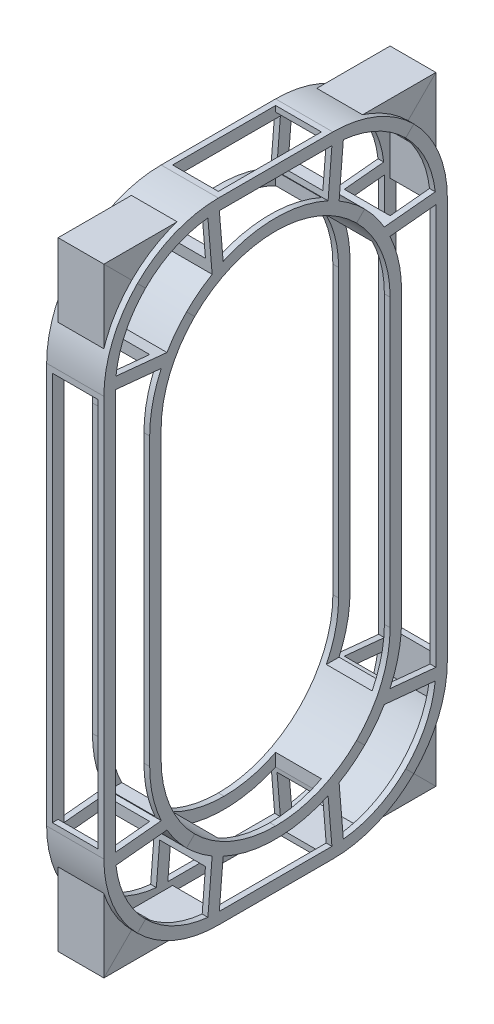
SolidWorks part; units mm, degrees
ref_plane "Front Plane" through (0, 0, 0) normal (0, 0, 1) x (1, 0, 0)
ref_plane "Top Plane" through (0, 0, 0) normal (0, 1, 0) x (1, 0, 0)
ref_plane "Right Plane" through (0, 0, 0) normal (1, 0, 0) x (0, 0, -1)
sketch "Sketch2" plane through (0, 0, 0) normal (0, 1, 0) x (1, 0, 0)
  line L0 (20, 20) -> (-20, 20)
  line L1 (25, -25) -> (-25, -25)
  line L2 (25, -25) -> (25, 25)
  line L3 (25, 25) -> (-25, 25)
  line L4 (-25, -25) -> (-25, 25)
  line L5 (25, -25) -> (-25, 25) construction
  line L6 (25, 25) -> (-25, -25) construction
  line L7 (-20, -20) -> (-20, 20)
  line L8 (20, -20) -> (-20, -20)
  line L9 (20, -20) -> (20, 20)
  point P0 (0, 0)
  dimension "D1" = 50
  dimension "D2" = 50
  dimension "D3" = 5
sketch "Sketch3" plane through (0, 0, 0) normal (1, 0, 0) x (0, 0, -1)
  line L0 (0, 0) -> (0, 500)
  line L2 (250, 500) -> (250, 0)
  line L3 (0, 500) -> (250, 500)
  line L4 (250, 0) -> (0, 0)
  dimension "D2" = 250
  dimension "D1" = 500
sweep "Sweep1" add profiles "Sketch2" path "Sketch3"
fillet "Fillet3" radius 100 8 edges at (0, 525, -275) (0, 25, -225) (0, -25, -275) (0, -25, 25) (0, 25, -25) (0, 475, -225) (0, 525, 25) (0, 475, -25)
sketch "Sketch5" plane through (0, -25, 0) normal (0, -1, 0) x (1, 0, 0)
  line L0 (-25, -125) -> (-17.5, -125) construction
  line L1 (-25, -175) -> (-25, -75) construction
  line L2 (25, -175) -> (25, -75) construction
  line L3 (0, -125) -> (25, -125) construction
  line L22 (-20, -170) -> (20, -170)
  line L23 (20, -170) -> (20, -80)
  line L24 (20, -80) -> (-20, -80)
  line L25 (-20, -80) -> (-20, -170)
  line L26 (-20, -170) -> (20, -170)
  line L27 (20, -170) -> (20, -80)
  line L28 (20, -80) -> (-20, -80)
  line L29 (-20, -80) -> (-20, -170)
  point P6 (0, -125)
  dimension "D1" = 5
extrude "Cut-Extrude2" cut sketch "Sketch5" against normal through all
sketch "Sketch6" plane through (0, 0, 25) normal (0, 0, 1) x (1, 0, 0)
  line L8 (-20, 420) -> (-20, 80)
  line L9 (-20, 80) -> (20, 80)
  line L10 (20, 80) -> (20, 420)
  line L11 (20, 420) -> (-20, 420)
  line L12 (-20, 420) -> (-20, 80)
  line L13 (-20, 80) -> (20, 80)
  line L14 (20, 80) -> (20, 420)
  line L15 (20, 420) -> (-20, 420)
  dimension "D1" = 5
extrude "Cut-Extrude3" cut sketch "Sketch6" against normal through all
sketch "Sketch19" plane through (-25, 0, 0) normal (-1, 0, 0) x (0, 0, 1)
  line L0 (-65.8391, -14.5326) -> (-69.5564, 29.9947)
  line L1 (14.4434, 65.0065) -> (-30.0951, 69.3847)
  line L2 (-65.8391, 514.5326) -> (-69.5564, 470.0053)
  line L3 (14.4434, 434.9935) -> (-30.0951, 430.6153)
  line L4 (-184.1609, 514.5326) -> (-180.4436, 470.0053)
  line L5 (-264.4434, 434.9935) -> (-219.9049, 430.6153)
  line L8 (-265, 425) -> (-265, 75)
  line L9 (-265, 425) -> (-265, 75)
  line L12 (-75, 515) -> (-175, 515)
  line L13 (-75.8348, 515) -> (-174.1652, 515)
  line L23 (-175, -15) -> (-75, -15)
  line L24 (15, 75) -> (15, 425)
  line L25 (-174.1652, -15) -> (-75.8348, -15)
  line L26 (15, 75) -> (15, 425)
  line L43 (-174.1652, 515) -> (-170.8258, 475)
  line L44 (-265, 425) -> (-224.8935, 421.0575)
  line L45 (-15, 125) -> (-15, 375)
  line L46 (-235, 375) -> (-235, 125)
  line L47 (-15, 125) -> (-15, 375)
  line L48 (-235, 375) -> (-235, 125)
  line L49 (-125, 515) -> (-125, -25) construction
  line L50 (-175, -25) -> (-75, -25) construction
  line L51 (-275, 250) -> (15, 250) construction
  line L52 (-275, 425) -> (-275, 75) construction
  line L53 (15, 425) -> (-25.1065, 421.0575)
  line L54 (-75.8348, 515) -> (-79.1742, 475)
  line L55 (15, 75) -> (-25.1065, 78.9425)
  line L56 (-75.8348, -15) -> (-79.1742, 25)
  line L57 (-174.1652, -15) -> (-170.8258, 25)
  line L58 (-265, 75) -> (-224.8935, 78.9425)
  line L71 (-264.4434, 65.0065) -> (-219.9049, 69.3847)
  line L72 (-184.1609, -14.5326) -> (-180.4436, 29.9947)
  line L73 (-264.0217, 65.048) -> (-223.9152, 68.9905) construction
  line L74 (-184.1305, -14.168) -> (-180.7911, 25.832) construction
  arc A0 (-219.9049, 69.3847) -> (-202.7817, 47.2183) centre (-125, 125) ccw
  arc A1 (-170.8258, 25) -> (-125, 15) centre (-125, 125) ccw
  arc A2 (14.4434, 65.0065) -> (-11.3604, 11.3604) centre (-75, 75) cw
  arc A3 (-11.3604, 11.3604) -> (-65.8391, -14.5326) centre (-75, 75) cw
  arc A4 (-47.2183, 47.2183) -> (-69.5564, 29.9947) centre (-125, 125) cw
  arc A5 (-30.0951, 69.3847) -> (-47.2183, 47.2183) centre (-125, 125) cw
  arc A6 (-11.3604, 488.6396) -> (-65.8391, 514.5326) centre (-75, 425) ccw
  arc A7 (14.4434, 434.9935) -> (-11.3604, 488.6396) centre (-75, 425) ccw
  arc A8 (-30.0951, 430.6153) -> (-47.2183, 452.7817) centre (-125, 375) ccw
  arc A9 (-47.2183, 452.7817) -> (-69.5564, 470.0053) centre (-125, 375) ccw
  arc A10 (-264.4434, 434.9935) -> (-238.6396, 488.6396) centre (-175, 425) cw
  arc A11 (-238.6396, 488.6396) -> (-184.1609, 514.5326) centre (-175, 425) cw
  arc A12 (-202.7817, 452.7817) -> (-180.4436, 470.0053) centre (-125, 375) cw
  arc A13 (-219.9049, 430.6153) -> (-202.7817, 452.7817) centre (-125, 375) cw
  arc A19 (-11.3604, 488.6396) -> (-75, 515) centre (-75, 425) ccw
  arc A20 (-265, 75) -> (-238.6396, 11.3604) centre (-175, 75) ccw
  arc A21 (-175, 515) -> (-238.6396, 488.6396) centre (-175, 425) ccw
  arc A22 (-238.6396, 488.6396) -> (-265, 425) centre (-175, 425) ccw
  arc A43 (-238.6396, 11.3604) -> (-175, -15) centre (-175, 75) ccw
  arc A44 (-75, -15) -> (-11.3604, 11.3604) centre (-75, 75) ccw
  arc A45 (-11.3604, 11.3604) -> (15, 75) centre (-75, 75) ccw
  arc A46 (15, 425) -> (-11.3604, 488.6396) centre (-75, 425) ccw
  arc A94 (-265, 75) -> (-238.6396, 11.3604) centre (-175, 75) ccw
  arc A95 (-264.4434, 65.0065) -> (-238.6396, 11.3604) centre (-175, 75) ccw
  arc A98 (-125, 485) -> (-202.7817, 452.7817) centre (-125, 375) ccw
  arc A99 (-47.2183, 452.7817) -> (-125, 485) centre (-125, 375) ccw
  arc A100 (-15, 375) -> (-47.2183, 452.7817) centre (-125, 375) ccw
  arc A101 (-47.2183, 47.2183) -> (-15, 125) centre (-125, 125) ccw
  arc A102 (-125, 15) -> (-47.2183, 47.2183) centre (-125, 125) ccw
  arc A103 (-202.7817, 47.2183) -> (-125, 15) centre (-125, 125) ccw
  arc A104 (-235, 125) -> (-202.7817, 47.2183) centre (-125, 125) ccw
  arc A105 (-202.7817, 452.7817) -> (-235, 375) centre (-125, 375) ccw
  arc A106 (-125, 485) -> (-170.8258, 475) centre (-125, 375) ccw
  arc A107 (-79.1742, 475) -> (-125, 485) centre (-125, 375) ccw
  arc A108 (-15, 375) -> (-25.1065, 421.0575) centre (-125, 375) ccw
  arc A109 (-25.1065, 78.9425) -> (-15, 125) centre (-125, 125) ccw
  arc A110 (-125, 15) -> (-79.1742, 25) centre (-125, 125) ccw
  arc A111 (-170.8258, 25) -> (-125, 15) centre (-125, 125) ccw
  arc A112 (-235, 125) -> (-224.8935, 78.9425) centre (-125, 125) ccw
  arc A113 (-224.8935, 421.0575) -> (-235, 375) centre (-125, 375) ccw
  arc A116 (-235, 125) -> (-202.7817, 47.2183) centre (-125, 125) ccw
  arc A117 (-202.7817, 47.2183) -> (-125, 15) centre (-125, 125) ccw
  arc A118 (-235, 125) -> (-224.8935, 78.9425) centre (-125, 125) ccw
  arc A119 (-202.7817, 47.2183) -> (-180.4436, 29.9947) centre (-125, 125) ccw
  arc A120 (-238.6396, 11.3604) -> (-175, -15) centre (-175, 75) ccw
  arc A121 (-238.6396, 11.3604) -> (-184.1609, -14.5326) centre (-175, 75) ccw
  line M25 (-245.7107, 495.7107) -> (-195.7107, 445.7107)
  line M28 (-54.2893, 445.7107) -> (-4.2893, 495.7107)
  dimension "D1" = 10
  dimension "D2" = 10
  dimension "D3" = 10
  dimension "D4" = 10
  dimension "D5" = 10
  dimension "D6" = 10
  dimension "D7" = 10
  dimension "D8" = 10
  dimension "D9" = 10
extrude "Cut-Extrude18" cut sketch "Sketch19" against normal through all contours A113 L44 L9 L58 A112 L48 | L5 A13 A10 M25 | A12 L4 A11 M25 | A107 L54 L13 L43 A106 | A9 A6 L2 M28 | A8 L3 A7 M28 | A109 L55 L26 L53 A108 L47 | L1 A5 A4 L0 A3 A2 | A110 A1 L57 L25 L56 | A95 A121 L72 A119 A0 L71
